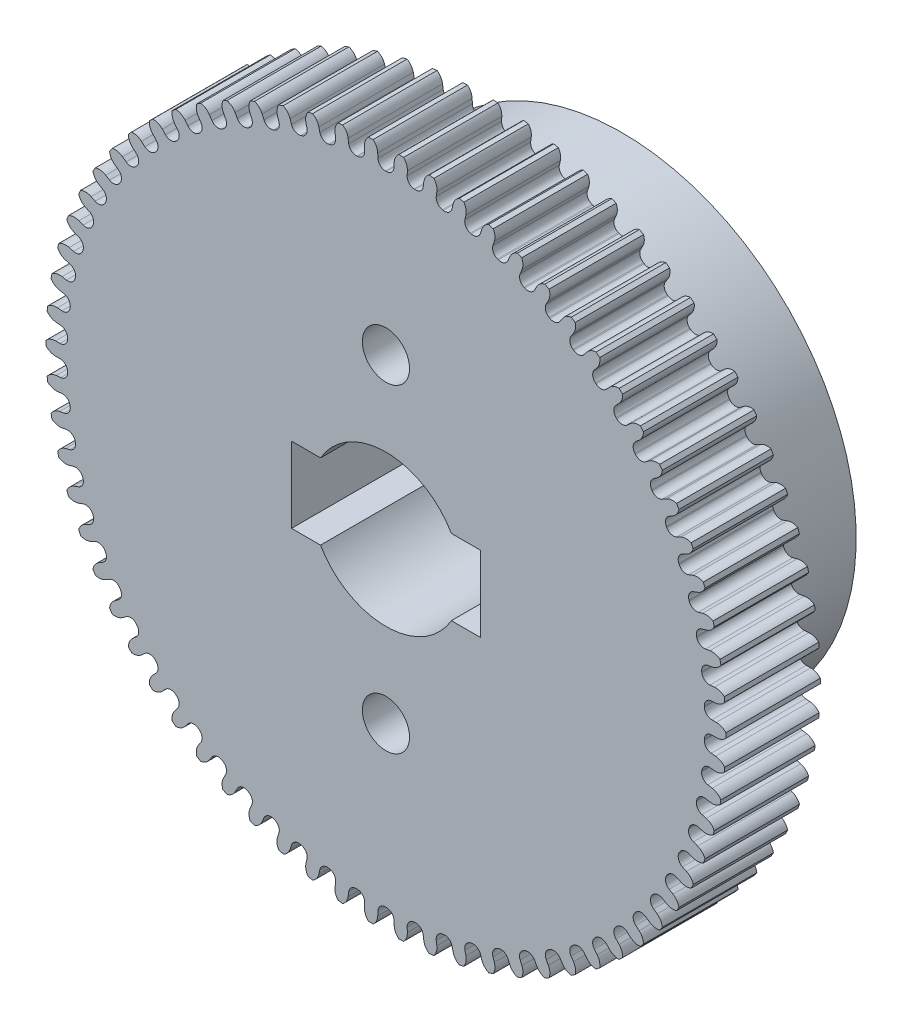
SolidWorks part; units mm, degrees
material "ABS"
ref_plane "Front Plane" through (0, 0, 0) normal (0, 0, 1) x (1, 0, 0)
ref_plane "Top Plane" through (0, 0, 0) normal (0, 1, 0) x (1, 0, 0)
ref_plane "Right Plane" through (0, 0, 0) normal (1, 0, 0) x (0, 0, -1)
sketch "Sketch1" plane through (0, 0, 0) normal (0, 0, 1) x (1, 0, 0)
  circle A0 centre (0, 0) radius 12.4
  dimension "D1" = 24.8
extrude "Boss-Extrude1" add sketch "Sketch1" along normal blind 28
sketch "Sketch2" plane through (0, 0, 28) normal (0, 0, 1) x (1, 0, 0)
  line L0 (-5.2361, -7.3692) -> (-6.7361, -9.9673)
  line L1 (-12, -0.85) -> (-9, -0.85)
  line L2 (-12, -0.85) -> (-12, 0.85)
  line L3 (-12, 0.85) -> (-9, 0.85)
  line L4 (-9, -0.85) -> (-9, 0.85)
  line L5 (-12, -0.85) -> (-9, 0.85) construction
  line L6 (-12, 0.85) -> (-9, -0.85) construction
  line L7 (9, -0.85) -> (12, -0.85)
  line L8 (9, -0.85) -> (9, 0.85)
  line L9 (9, 0.85) -> (12, 0.85)
  line L10 (12, -0.85) -> (12, 0.85)
  line L11 (9, -0.85) -> (12, 0.85) construction
  line L12 (9, 0.85) -> (12, -0.85) construction
  line L13 (-5.2361, -7.3692) -> (-3.7639, -8.2192)
  line L14 (-6.7361, -9.9673) -> (-5.2639, -10.8173)
  line L15 (-3.7639, -8.2192) -> (-5.2639, -10.8173)
  line L16 (-5.2361, -7.3692) -> (-5.2639, -10.8173) construction
  line L17 (-6.7361, -9.9673) -> (-3.7639, -8.2192) construction
  line L18 (3.7639, -8.2192) -> (5.2639, -10.8173)
  line L19 (3.7639, -8.2192) -> (5.2361, -7.3692)
  line L20 (5.2639, -10.8173) -> (6.7361, -9.9673)
  line L21 (5.2361, -7.3692) -> (6.7361, -9.9673)
  line L22 (3.7639, -8.2192) -> (6.7361, -9.9673) construction
  line L23 (5.2639, -10.8173) -> (5.2361, -7.3692) construction
  line L24 (-5.25, -9.0933) -> (0, 0) construction
  line L25 (0, 0) -> (0, -8.656) construction
  line L26 (5.25, -9.0933) -> (0, 0) construction
  line L27 (-7, 10.2352) -> (-7, 7.8262)
  line L28 (7, 10.2352) -> (7, 7.8262)
  circle A0 centre (0, 0) radius 10.5
  circle A1 centre (0, 0) radius 12.4 construction
  point P3 (-10.5, 0)
  point P8 (10.5, 0)
  point P14 (-5.25, -9.0933)
  point P15 (5.25, -9.0933)
  circle M19 centre (0, 0) radius 12.4
  dimension "D1" = 21
  dimension "D2" = 30
  dimension "D3" = 30
  dimension "D4" = 1.7
  dimension "D5" = 3
  dimension "D6" = 14
extrude "Cut-Extrude1" cut sketch "Sketch2" against normal blind 30 contours L9 A0 L3 L4 L1 L0 L13 L15 L18 L19 L21 L7 L8 | L0 A0 L15 L13 | L18 A0 L21 L19 region at (-4.8721, -8.4388, 28) region at (0, 0.127, 28) region at (4.8721, -8.4388, 28)
sketch "Sketch3" plane through (0, 0, 0) normal (0, 0, 1) x (1, 0, 0)
  circle A0 centre (0, 0) radius 3.2
  circle A1 centre (0, 0) radius 4.5
  point P8 (0, 0)
  dimension "D1" = 6.4
  dimension "D2" = 9
  dimension "D3" = 0
extrude "Boss-Extrude2" add sketch "Sketch3" along normal blind 6
sketch "Sketch4" plane through (0, 0, 0) normal (0, 0, -1) x (-1, 0, 0)
  line L0 (-6.2, 10.7387) -> (6.2, -10.7387)
  line L1 (6.2, 10.7387) -> (-6.2, -10.7387)
  line L2 (0, 8.9491) -> (0, -6.5324) construction
  line L3 (-6.2, 10.7387) -> (-6.2, -10.7387)
  line L4 (6.2, 10.7387) -> (6.2, -10.7387)
  circle A0 centre (0, 0) radius 12.4 construction
  circle A1 centre (0, 0) radius 12.4
  circle A2 centre (0, 0) radius 10.5
  dimension "D1" = 21
  dimension "D2" = 30
  dimension "D3" = 30
extrude "Cut-Extrude2" cut sketch "Sketch2<3>" against normal blind 18 contours A0 L28 L27 M19 region at (0, 10.6333, 28)
sketch "Sketch2<3>" plane through (0, 0, 28) normal (0, 0, 1) x (1, 0, 0) same geometry as "Sketch2"
sketch "Sketch5" plane through (0, 0, 0) normal (0, 0, -1) x (-1, 0, 0)
  circle A1 centre (0, 0) radius 12.4
  circle A2 centre (0, 0) radius 12.4
  dimension "D1" = 0
extrude "Boss-Extrude3" add sketch "Sketch5" along normal blind 28
sketch "Sketch6" plane through (0, 0, -28) normal (0, 0, -1) x (-1, 0, 0)
  circle A0 centre (0, 0) radius 4.5
  dimension "D1" = 9
extrude "Cut-Extrude3" cut sketch "Sketch6" against normal blind 26
sketch "Sketch7" plane through (0, 0, 0) normal (0, 1, 0) x (1, 0, 0)
  line L0 (4.5, 2) -> (4.5, 28) construction
  line L1 (-4.5, 2) -> (4.5, 2)
  line L2 (-4.5, 2) -> (-4.5, 8)
  line L3 (-4.5, 8) -> (4.5, 8)
  line L4 (4.5, 2) -> (4.5, 8)
  point P3 (0, 0)
  dimension "D3" = 6
extrude "Cut-Extrude4" cut sketch "Sketch7" against normal through all both and the other way through all
sketch "Sketch10" plane through (0, 0, 0) normal (0, 0, 1) x (1, 0, 0)
  line L1 (-0.75, 2.2) -> (0.75, 2.2)
  line L2 (-0.75, 2.2) -> (-0.75, 4.2)
  line L3 (-0.75, 4.2) -> (0.75, 4.2)
  line L4 (0.75, 2.2) -> (0.75, 4.2)
  line L5 (-0.75, 2.2) -> (0.75, 4.2) construction
  line L6 (-0.75, 4.2) -> (0.75, 2.2) construction
  line L12 (10.4655, -0.85) -> (9, -0.85)
  line L13 (9, -0.85) -> (9, 0.85)
  line L14 (9, 0.85) -> (10.4655, 0.85)
  line L15 (-10.4655, 0.85) -> (-9, 0.85)
  line L16 (-9, 0.85) -> (-9, -0.85)
  line L17 (-9, -0.85) -> (-10.4655, -0.85)
  line L24 (10.4655, -0.85) -> (9, -0.85)
  line L25 (9, -0.85) -> (9, 0.85)
  line L26 (9, 0.85) -> (10.4655, 0.85)
  line L27 (-10.4655, 0.85) -> (-9, 0.85)
  line L28 (-9, 0.85) -> (-9, -0.85)
  line L29 (-9, -0.85) -> (-10.4655, -0.85)
  circle A0 centre (0, 0) radius 3.2 construction
  circle A1 centre (0, 0) radius 3.2
  arc A4 (10.4655, 0.85) -> (-10.4655, 0.85) centre (0, 0) ccw
  arc A5 (-10.4655, -0.85) -> (10.4655, -0.85) centre (0, 0) ccw
  arc A8 (10.4655, 0.85) -> (-10.4655, 0.85) centre (0, 0) ccw
  arc A9 (-10.4655, -0.85) -> (10.4655, -0.85) centre (0, 0) ccw
  point P15 (0, 3.2)
  point P16 (0, 0)
  point P20 (0, 3.2)
  dimension "D2" = 1.5
  dimension "D3" = 2
  dimension "D1" = 0
sketch "Sketch11" plane through (0, 0, 0) normal (0, 0, 1) x (1, 0, 0)
  circle A0 centre (0, 0) radius 1.25
  dimension "D1" = 2.5
extrude "Cut-Extrude6" cut sketch "Sketch11" against normal through all both and the other way through all
ref_plane "Plane1" through (0, 0, -24) normal (0, 0, -1) x (-1, 0, 0)
sketch "Sketch12" plane through (0, 0, -24) normal (0, 0, -1) x (-1, 0, 0)
  circle A0 centre (0, 0) radius 4.5 construction
  circle A1 centre (0, 0) radius 4.5
  circle A2 centre (0, 0) radius 4
  dimension "D1" = 8
extrude "Boss-Extrude5" add sketch "Sketch12" against normal up to surface (16 mm away) up to face at (0, 7.1137, -8)
ref_plane "Plane2" through (0, 0, -20.5) normal (0, 0, -1) x (-1, 0, 0)
sketch "Sketch13" plane through (0, 0, -20.5) normal (0, 0, -1) x (-1, 0, 0)
  circle A0 centre (0, 0) radius 18
  circle A1 centre (0, 0) radius 4.5 construction
  circle A2 centre (0, 0) radius 4.5
  dimension "D1" = 36
extrude "Boss-Extrude6" add sketch "Sketch13" against normal blind 5
sketch "Sketch14" plane through (0, 0, -28) normal (0, 0, -1) x (-1, 0, 0)
  line L0 (-0.8076, 17.9819) -> (0, 0)
  line L1 (0, 0) -> (0.8076, 17.9819)
  line L2 (-0.4354, 17.4946) -> (-0.4073, 16.8701)
  line L3 (0.4073, 16.8701) -> (0.4354, 17.4946)
  circle A0 centre (0, 0) radius 17.5 construction
  circle A1 centre (0, 0) radius 16.875 construction
  circle A2 centre (0, 0) radius 18 construction
  arc A3 (-0.8076, 17.9819) -> (-0.6827, 17.987) centre (0, 0) cw
  arc A4 (0.8076, 17.9819) -> (0.6827, 17.987) centre (0, 0) ccw
  arc A5 (-0.4073, 16.8701) -> (0.4073, 16.8701) centre (0, 0) cw
  arc A6 (-0.4354, 17.4946) -> (-0.6827, 17.987) centre (-1.1096, 17.4643) ccw
  arc A7 (0.4354, 17.4946) -> (0.6827, 17.987) centre (1.1096, 17.4643) cw
  arc A8 (-0.6827, 17.987) -> (0.6827, 17.987) centre (0, 0) cw
  point P15 (-0.7851, 17.4824)
  point P17 (0.7851, 17.4824)
  dimension "D1" = 35
  dimension "D2" = 33.75
  dimension "D3" = 1.5708
  dimension "D4" = 0.35
  dimension "D5" = 0.125
extrude "Cut-Extrude7" cut sketch "Sketch14" against normal up to surface (12.5 mm away) contours L3 A7 A6 L2 A5 region at (0, 17.4748, -28) up to face at (-12.4, 0, -15.5)
fillet "Fillet1" radius 0.4 2 edges at (-0.4073, 16.8701, -18) (0.4073, 16.8701, -18)
sketch "Sketch15" plane through (0, 0, 0) normal (0, 1, 0) x (1, 0, 0)
  line L0 (0, 0) -> (0, 27.0361) construction
pattern_circular "CirPattern1" count 70 over 360 about axis through (0, 0, 0) along (0, 0, -1) of "Cut-Extrude7", "Fillet1" reverse direction yes
sketch "Sketch16" plane through (0, 0, 0) normal (0, 1, 0) x (1, 0, 0)
  line L1 (-12.4, -28) -> (12.4, -28)
  line L2 (-12.4, -28) -> (-12.4, 15.5)
  line L3 (-12.4, 15.5) -> (12.4, 15.5)
  line L4 (12.4, -28) -> (12.4, 15.5)
extrude "Cut-Extrude8" cut sketch "Sketch16" against normal through all both and the other way through all
sketch "Sketch17" plane through (0, 0, -28) normal (0, 0, -1) x (-1, 0, 0)
  line L1 (-5, -2) -> (5, -2)
  line L2 (-5, -2) -> (-5, 2)
  line L3 (-5, 2) -> (5, 2)
  line L4 (5, -2) -> (5, 2)
  line L5 (-5, -2) -> (5, 2) construction
  line L6 (-5, 2) -> (5, -2) construction
  point P0 (0, 0)
  dimension "D1" = 4
  dimension "D2" = 10
extrude "Cut-Extrude9" cut sketch "Sketch17" against normal through all
sketch "Sketch18" plane through (0, 0, -28) normal (0, 0, -1) x (-1, 0, 0)
  line L0 (0, 4.5) -> (0, 12.4)
  line L2 (0, 12.4) -> (0, 10.95)
  line L3 (0, 4.5) -> (0, 5.95)
  line L4 (0, -4.5) -> (0, -5.95)
  line L5 (0, -12.4) -> (0, -10.95)
  line L6 (0, -5.95) -> (0, -10.95)
  line L7 (0, 4.5) -> (0, -4.5)
  arc A2 (4.0311, 2) -> (-4.0311, 2) centre (0, 0) ccw construction
  circle A3 centre (0, 0) radius 12.4 construction
  circle A4 centre (0, 8.45) radius 2.5
  arc A5 (-4.0311, -2) -> (4.0311, -2) centre (0, 0) ccw construction
  circle A6 centre (0, 0) radius 12.4 construction
  circle A7 centre (0, -8.45) radius 2.5
  dimension "D1" = 1.45
  dimension "D2" = 1.45
  dimension "D3" = 1.45
  dimension "D4" = 1.45
extrude "Cut-Extrude10" cut sketch "Sketch18" against normal blind 8.5 contours L0 A4 | L0 A4 | L6 A7 | L6 A7 region at (1.061, 8.45, -28) region at (-1.061, 8.45, -28) region at (-1.061, -8.45, -28) region at (1.061, -8.45, -28)
sketch "Sketch20" plane through (0, 0, -19.5) normal (0, 0, -1) x (-1, 0, 0)
  circle A0 centre (0, 8.45) radius 1.25
  circle A1 centre (0, -8.45) radius 1.25
extrude "Cut-Extrude11" cut sketch "Sketch20" against normal blind 4
